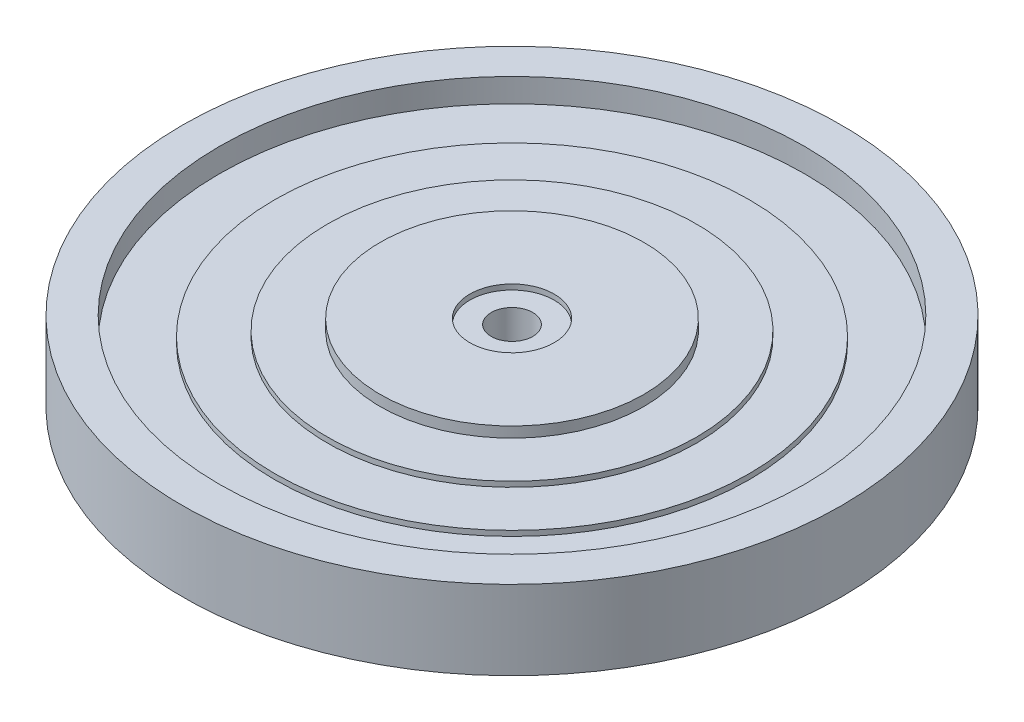
SolidWorks part; units mm, degrees
material "AISI 316 Stainless Steel Sheet (SS)"
ref_plane "Front Plane" through (0, 0, 0) normal (0, 0, 1) x (1, 0, 0)
ref_plane "Top Plane" through (0, 0, 0) normal (0, 1, 0) x (1, 0, 0)
ref_plane "Right Plane" through (0, 0, 0) normal (1, 0, 0) x (0, 0, -1)
ref_axis "Axis1" through (0, 111.76, 0) along (0, -1, 0)
sketch "Sketch3" plane through (0, 0, 0) normal (0, 0, 1) x (1, 0, 0)
  line L4 (79.375, -9.525) -> (79.375, 9.525)
  line L8 (73.025, 9.525) -> (73.025, -9.525) construction
  line L10 (0, -47.5021) -> (0, 47.5021) construction
  line L11 (0, 0) -> (79.375, 0) construction
  line L14 (5.009, 7.62) -> (5.009, -7.62)
  line L42 (70.485, -3.81) -> (70.485, -9.525)
  line L43 (70.485, -9.525) -> (73.025, -9.525)
  line L44 (73.025, -9.525) -> (79.375, -9.525)
  line L45 (79.375, 9.525) -> (73.025, 9.525)
  line L46 (73.025, 9.525) -> (70.485, 9.525)
  line L47 (5.009, 7.62) -> (10.16, 7.62)
  line L48 (70.485, 9.525) -> (70.485, 3.81)
  line L53 (57.15, 3.81) -> (70.485, 3.81)
  line L54 (5.009, -7.62) -> (10.16, -7.62)
  line L58 (57.15, -3.81) -> (70.485, -3.81)
  line L59 (31.75, 6.35) -> (44.45, 6.35)
  line L60 (44.45, 6.35) -> (44.45, 5.08)
  line L61 (44.45, 5.08) -> (57.15, 5.08)
  line L62 (57.15, 5.08) -> (57.15, 3.81)
  line L63 (31.75, -6.35) -> (44.45, -6.35)
  line L64 (44.45, -6.35) -> (44.45, -5.08)
  line L65 (44.45, -5.08) -> (57.15, -5.08)
  line L66 (57.15, -5.08) -> (57.15, -3.81)
  line L68 (10.16, 8.89) -> (31.75, 8.89)
  line L69 (31.75, 8.89) -> (31.75, 6.35)
  line L71 (10.16, -8.89) -> (31.75, -8.89)
  line L72 (31.75, -8.89) -> (31.75, -6.35)
  line L73 (10.16, 8.89) -> (10.16, 7.62)
  line L74 (10.16, -7.62) -> (10.16, -8.89)
  point P11 (0, 0)
  dimension "D4" = 19.05
  dimension "D2" = 73.025
  dimension "D6" = 79.375
  dimension "D3" = 5.009
  dimension "D8" = 15.24
  dimension "D1" = 2.54
  dimension "D5" = 7.62
  dimension "D9" = 12.7
  dimension "D10" = 10.16
  dimension "D11" = 44.45
  dimension "D12" = 57.15
  dimension "D7" = 31.75
  dimension "D14" = 17.78
  dimension "D13" = 10.16
revolve "Revolve1" add sketch "Sketch3" angle 360 about L10 region at (39.5773, 0, 0)
sketch "Stock Sketch" plane through (0, 0, 0) normal (0, -1, 0) x (1, 0, 0)
  line L1 (-101.6, -101.6) -> (101.6, -101.6)
  line L2 (-101.6, -101.6) -> (-101.6, 101.6)
  line L3 (-101.6, 101.6) -> (101.6, 101.6)
  line L4 (101.6, -101.6) -> (101.6, 101.6)
  line L5 (-101.6, -101.6) -> (101.6, 101.6) construction
  line L6 (-101.6, 101.6) -> (101.6, -101.6) construction
  point P0 (0, 0)
  dimension "D1" = 203.2
ref_plane "Blade Plane" through (79.375, 0, 0) normal (1, 0, 0) x (0, 0, -1)
sketch "Sketch4" plane through (0, 0, 0) normal (0, 1, 0) x (1, 0, 0)
  line L0 (69.85, 79.375) -> (0, 79.375) construction
  line L1 (79.375, 0) -> (79.375, 69.85) construction
  line L2 (0, 0) -> (0, -79.375) construction
  circle A0 centre (69.85, 69.85) radius 9.525
  circle A1 centre (0, 0) radius 79.375 construction
  circle A2 centre (-69.85, 69.85) radius 9.525
  dimension "D1" = 19.05
equation "\"D6@Sketch3\"=\"rotor tip@[TP] [Turb] Turbine.Assembly\""
equation "\"D2@Sketch3\"=\"rotor base@[TP] [Turb] Turbine.Assembly\""
equation "\"D4@Sketch3\"=\"blade width@[TP] [Turb] Turbine.Assembly\""
